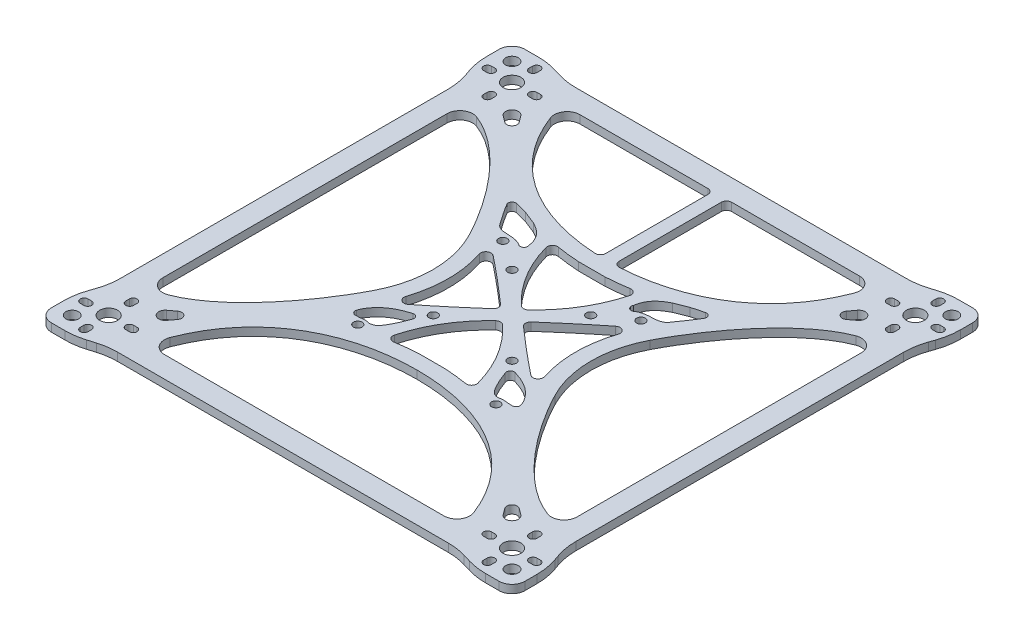
SolidWorks part; units mm, degrees
ref_plane "Front Plane" through (0, 0, 0) normal (0, 0, 1) x (1, 0, 0)
ref_plane "Top Plane" through (0, 0, 0) normal (0, 1, 0) x (1, 0, 0)
ref_plane "Right Plane" through (0, 0, 0) normal (1, 0, 0) x (0, 0, -1)
sketch "Sketch2" plane through (0, 0, 0) normal (0, 1, 0) x (1, 0, 0)
  line L1 (-91.75, 91.75) -> (91.75, 91.75)
  line L2 (-91.75, 91.75) -> (-91.75, -91.75)
  line L3 (-91.75, -91.75) -> (91.75, -91.75)
  line L4 (91.75, 91.75) -> (91.75, -91.75)
  line L5 (-91.75, 91.75) -> (91.75, -91.75) construction
  line L6 (-91.75, -91.75) -> (91.75, 91.75) construction
  point P0 (0, 0)
  dimension "D1" = 183.5
extrude "Base size" add sketch "Sketch2" along normal blind 3.15
sketch "Sketch3" plane through (0, 3.15, 0) normal (0, 1, 0) x (1, 0, 0)
  line L0 (-91.75, 91.75) -> (-91.75, -91.75) construction
  line L1 (80.25, 80.5) -> (-80.25, 80.5)
  line L2 (80.25, 80.5) -> (80.25, -80.5)
  line L3 (80.25, -80.5) -> (-80.25, -80.5)
  line L4 (-80.25, 80.5) -> (-80.25, -80.5)
  line L5 (80.25, 80.5) -> (-80.25, -80.5) construction
  line L6 (80.25, -80.5) -> (-80.25, 80.5) construction
  line L7 (0, 91.75) -> (0, -91.75) construction
  line L8 (-91.75, 0) -> (91.75, 0) construction
  line L9 (-91.75, -88.75) -> (91.75, -88.75)
  line L10 (80.25, 61.3098) -> (-80.25, -61.3098) construction
  line L11 (-91.75, 36.75) -> (91.75, 36.75) construction
  line L12 (88.25, 91.75) -> (88.25, -91.75)
  line L13 (91.75, -91.75) -> (91.75, 91.75) construction
  line L14 (-77.75, 91.75) -> (-67.75, 88.75)
  line L15 (-91.75, 77.75) -> (-88.25, 67.75)
  line L16 (-67.75, 88.75) -> (-67.75, 80.5) construction
  line L17 (-91.75, 88.75) -> (91.75, 88.75)
  line L18 (-88.25, 91.75) -> (-88.25, -91.75)
  line L19 (91.75, 91.75) -> (-91.75, 91.75) construction
  line L20 (-91.75, -91.75) -> (91.75, -91.75) construction
  line L21 (-67.75, 84.625) -> (-77.75, 84.625) construction
  line L22 (-77.75, 91.75) -> (-77.75, 80.5) construction
  line L23 (-91.75, 77.75) -> (-80.25, 77.75) construction
  line L24 (-88.25, 67.75) -> (-80.25, 67.75) construction
  line L25 (-84.25, 67.75) -> (-84.25, 77.75) construction
  line L26 (77.75, 91.75) -> (67.75, 88.75)
  line L27 (91.75, 77.75) -> (88.25, 67.75)
  line L28 (91.75, -77.75) -> (88.25, -67.75)
  line L29 (77.75, -91.75) -> (67.75, -88.75)
  line L30 (-77.75, -91.75) -> (-67.75, -88.75)
  line L31 (-91.75, -77.75) -> (-88.25, -67.75)
  line L32 (-61, 80.5) -> (61, -80.5) construction
  line L33 (61, 80.5) -> (-61, -80.5) construction
  line L34 (0, 36.75) -> (0, -36.75)
  line L35 (-28, 0) -> (28, 0)
  line L36 (2.6, 80.5) -> (2.6, 36.7902)
  line L37 (28, 80.5) -> (28, -91.75) construction
  line L38 (-61, 80.5) -> (61, 80.5) construction
  line L39 (-2.6, 80.5) -> (-2.6, 36.7902)
  line L40 (-80.3099, 61.2501) -> (80.3099, -61.2501) construction
  line L41 (80.25, 61.3098) -> (80.3099, -61.2501) construction
  line L42 (61, 80.5) -> (80.25, 61.3098) construction
  line L43 (-84.25, 77.75) -> (-84.25, 91.75) construction
  line L44 (-77.75, 84.625) -> (-91.75, 84.625) construction
  line L45 (-61, -80.5) -> (-61, -88.75) construction
  line L46 (61, -80.5) -> (61, -88.75) construction
  line L47 (-61, -84.625) -> (61, -84.625) construction
  line L48 (34.054, 44.9401) -> (44.8339, 34.1936) construction
  spline S0 degree 3 poles (61, 80.5) (52.8169, 49.5684) (26.9144, 36.75) (0, 36.75) knots 0 0 0 0 1 1 1 1
  spline S1 degree 3 poles (80.25, 61.3098) (57.9285, 59.6828) (32.235, 20.0435) (28, 0) knots 0 0 0 0 1 1 1 1
  spline S2 degree 3 poles (-61, 80.5) (-52.8169, 49.5684) (-26.9144, 36.75) (0, 36.75) knots 0 0 0 0 1 1 1 1
  spline S3 degree 3 poles (-61, -80.5) (-52.8169, -49.5684) (-26.9144, -36.75) (0, -36.75) knots 0 0 0 0 1 1 1 1
  spline S4 degree 3 poles (61, -80.5) (52.8169, -49.5684) (26.9144, -36.75) (0, -36.75) knots 0 0 0 0 1 1 1 1
  spline S5 degree 3 poles (80.25, -61.3098) (57.9285, -59.6828) (32.235, -20.0435) (28, 0) knots 0 0 0 0 1 1 1 1
  spline S6 degree 3 poles (-80.25, 61.3098) (-57.9285, 59.6828) (-32.235, 20.0435) (-28, 0) knots 0 0 0 0 1 1 1 1
  spline S7 degree 3 poles (-80.25, -61.3098) (-57.9285, -59.6828) (-32.235, -20.0435) (-28, 0) knots 0 0 0 0 1 1 1 1
  point P0 (0, 0)
  point P82 (39.444, 39.5668)
  line M13 (91.75, -91.75) -> (91.75, 91.75)
  line M14 (91.75, 91.75) -> (-91.75, 91.75)
  line M15 (-91.75, 91.75) -> (-91.75, -91.75)
  line M16 (-91.75, -91.75) -> (91.75, -91.75)
  dimension "D2" = 176.5
  dimension "D3" = 177.5
  dimension "D4" = 10
  dimension "D5" = 14
  dimension "D6" = 5.2
  dimension "D7" = 122
  dimension "D8" = 73.5
  dimension "D9" = 8.25
  dimension "D10" = 8
  dimension "D11" = 56
extrude "Base outline and pockets" cut sketch "Sketch3" against normal up to next contours L1 S2 L39 | S0 L1 L36 | L26 L14 L17 M14 | L4 | L2 S1 | L3 S4 S3 | L31 L18 L15 M15 | L30 L29 L9 M16 | L28 L27 L12 M13 region at (26.4341, 3.15, -62.2428) region at (60.1835, 3.15, 0) region at (-26.4341, 3.15, -62.2428) region at (0, 3.15, 62.0397) region at (-60.1835, 3.15, 0) region at (0, 3.15, 90.2844) region at (-90.0401, 3.15, 0) region at (90.0401, 3.15, 0) region at (0, 3.15, -90.2844)
sketch "Sketch4" plane through (0, 3.15, 0) normal (0, 1, 0) x (1, 0, 0)
  line L0 (0, 88.75) -> (0, -88.75) construction
  line L1 (-67.75, 88.75) -> (67.75, 88.75) construction
  line L2 (-67.75, -88.75) -> (67.75, -88.75) construction
  line L3 (-88.25, 0) -> (88.25, 0) construction
  line L4 (-88.25, 67.75) -> (-88.25, -67.75) construction
  line L5 (88.25, 67.75) -> (88.25, -67.75) construction
  line L6 (91.75, 91.75) -> (-91.75, -91.75) construction
  line L7 (-91.75, 91.75) -> (91.75, -91.75) construction
  line L8 (74.6853, 78.1353) -> (81.5853, 78.1353) construction
  line L9 (60.3295, 78.1353) -> (91.8849, 78.1353) construction
  line L10 (91.75, 77.75) -> (88.25, 67.75) construction
  line L11 (78.1353, 91.8656) -> (78.1353, 61.0454) construction
  line L12 (77.75, 91.75) -> (67.75, 88.75) construction
  line L13 (68.6353, 78.1353) -> (70.0103, 78.1353) construction
  line L14 (68.6353, 79.6353) -> (70.0103, 79.6353)
  line L15 (68.6353, 76.6353) -> (70.0103, 76.6353)
  line L16 (71.5103, 78.1353) -> (71.5103, 76.6353) construction
  line L17 (71.5103, 76.6353) -> (67.1353, 76.6353) construction
  line L18 (67.1353, 78.1353) -> (67.1353, 76.6353) construction
  line L19 (87.6353, 78.1353) -> (86.2603, 78.1353) construction
  line L20 (87.6353, 79.6353) -> (86.2603, 79.6353)
  line L21 (87.6353, 76.6353) -> (86.2603, 76.6353)
  line L22 (78.1353, 68.6353) -> (78.1353, 70.0103) construction
  line L23 (79.6353, 68.6353) -> (79.6353, 70.0103)
  line L24 (76.6353, 68.6353) -> (76.6353, 70.0103)
  line L25 (78.1353, 87.6353) -> (78.1353, 86.2603) construction
  line L26 (79.6353, 87.6353) -> (79.6353, 86.2603)
  line L27 (76.6353, 87.6353) -> (76.6353, 86.2603)
  line L28 (-68.6353, 78.1353) -> (-70.0103, 78.1353) construction
  line L29 (-68.6353, 79.6353) -> (-70.0103, 79.6353)
  line L30 (-68.6353, 76.6353) -> (-70.0103, 76.6353)
  line L31 (-78.1353, 87.6353) -> (-78.1353, 86.2603) construction
  line L32 (-79.6353, 87.6353) -> (-79.6353, 86.2603)
  line L33 (-76.6353, 87.6353) -> (-76.6353, 86.2603)
  line L34 (-87.6353, 78.1353) -> (-86.2603, 78.1353) construction
  line L35 (-87.6353, 79.6353) -> (-86.2603, 79.6353)
  line L36 (-87.6353, 76.6353) -> (-86.2603, 76.6353)
  line L37 (-78.1353, 68.6353) -> (-78.1353, 70.0103) construction
  line L38 (-79.6353, 68.6353) -> (-79.6353, 70.0103)
  line L39 (-76.6353, 68.6353) -> (-76.6353, 70.0103)
  line L40 (-87.6353, -78.1353) -> (-86.2603, -78.1353) construction
  line L41 (-87.6353, -79.6353) -> (-86.2603, -79.6353)
  line L42 (-87.6353, -76.6353) -> (-86.2603, -76.6353)
  line L43 (-78.1353, -68.6353) -> (-78.1353, -70.0103) construction
  line L44 (-79.6353, -68.6353) -> (-79.6353, -70.0103)
  line L45 (-76.6353, -68.6353) -> (-76.6353, -70.0103)
  line L46 (-68.6353, -78.1353) -> (-70.0103, -78.1353) construction
  line L47 (-68.6353, -79.6353) -> (-70.0103, -79.6353)
  line L48 (-68.6353, -76.6353) -> (-70.0103, -76.6353)
  line L49 (-78.1353, -87.6353) -> (-78.1353, -86.2603) construction
  line L50 (-79.6353, -87.6353) -> (-79.6353, -86.2603)
  line L51 (-76.6353, -87.6353) -> (-76.6353, -86.2603)
  line L52 (68.6353, -78.1353) -> (70.0103, -78.1353) construction
  line L53 (68.6353, -79.6353) -> (70.0103, -79.6353)
  line L54 (68.6353, -76.6353) -> (70.0103, -76.6353)
  line L55 (78.1353, -87.6353) -> (78.1353, -86.2603) construction
  line L56 (79.6353, -87.6353) -> (79.6353, -86.2603)
  line L57 (76.6353, -87.6353) -> (76.6353, -86.2603)
  line L58 (87.6353, -78.1353) -> (86.2603, -78.1353) construction
  line L59 (87.6353, -79.6353) -> (86.2603, -79.6353)
  line L60 (87.6353, -76.6353) -> (86.2603, -76.6353)
  line L61 (78.1353, -68.6353) -> (78.1353, -70.0103) construction
  line L62 (79.6353, -68.6353) -> (79.6353, -70.0103)
  line L63 (76.6353, -68.6353) -> (76.6353, -70.0103)
  circle A0 centre (78.1353, 78.1353) radius 3.45
  arc A1 (68.6353, 79.6353) -> (68.6353, 76.6353) centre (68.6353, 78.1353) ccw
  arc A2 (70.0103, 76.6353) -> (70.0103, 79.6353) centre (70.0103, 78.1353) ccw
  arc A3 (87.6353, 79.6353) -> (87.6353, 76.6353) centre (87.6353, 78.1353) cw
  arc A4 (86.2603, 76.6353) -> (86.2603, 79.6353) centre (86.2603, 78.1353) cw
  arc A5 (79.6353, 68.6353) -> (76.6353, 68.6353) centre (78.1353, 68.6353) cw
  arc A6 (76.6353, 70.0103) -> (79.6353, 70.0103) centre (78.1353, 70.0103) cw
  arc A7 (79.6353, 87.6353) -> (76.6353, 87.6353) centre (78.1353, 87.6353) ccw
  arc A8 (76.6353, 86.2603) -> (79.6353, 86.2603) centre (78.1353, 86.2603) ccw
  arc A9 (-68.6353, 79.6353) -> (-68.6353, 76.6353) centre (-68.6353, 78.1353) cw
  arc A10 (-70.0103, 76.6353) -> (-70.0103, 79.6353) centre (-70.0103, 78.1353) cw
  arc A11 (-79.6353, 87.6353) -> (-76.6353, 87.6353) centre (-78.1353, 87.6353) cw
  arc A12 (-76.6353, 86.2603) -> (-79.6353, 86.2603) centre (-78.1353, 86.2603) cw
  arc A13 (-87.6353, 79.6353) -> (-87.6353, 76.6353) centre (-87.6353, 78.1353) ccw
  arc A14 (-86.2603, 76.6353) -> (-86.2603, 79.6353) centre (-86.2603, 78.1353) ccw
  arc A15 (-79.6353, 68.6353) -> (-76.6353, 68.6353) centre (-78.1353, 68.6353) ccw
  arc A16 (-76.6353, 70.0103) -> (-79.6353, 70.0103) centre (-78.1353, 70.0103) ccw
  circle A17 centre (-78.1353, 78.1353) radius 3.45
  arc A18 (-87.6353, -79.6353) -> (-87.6353, -76.6353) centre (-87.6353, -78.1353) cw
  arc A19 (-86.2603, -76.6353) -> (-86.2603, -79.6353) centre (-86.2603, -78.1353) cw
  arc A20 (-79.6353, -68.6353) -> (-76.6353, -68.6353) centre (-78.1353, -68.6353) cw
  arc A21 (-76.6353, -70.0103) -> (-79.6353, -70.0103) centre (-78.1353, -70.0103) cw
  arc A22 (-68.6353, -79.6353) -> (-68.6353, -76.6353) centre (-68.6353, -78.1353) ccw
  arc A23 (-70.0103, -76.6353) -> (-70.0103, -79.6353) centre (-70.0103, -78.1353) ccw
  arc A24 (-79.6353, -87.6353) -> (-76.6353, -87.6353) centre (-78.1353, -87.6353) ccw
  arc A25 (-76.6353, -86.2603) -> (-79.6353, -86.2603) centre (-78.1353, -86.2603) ccw
  arc A26 (68.6353, -79.6353) -> (68.6353, -76.6353) centre (68.6353, -78.1353) cw
  arc A27 (70.0103, -76.6353) -> (70.0103, -79.6353) centre (70.0103, -78.1353) cw
  arc A28 (79.6353, -87.6353) -> (76.6353, -87.6353) centre (78.1353, -87.6353) cw
  arc A29 (76.6353, -86.2603) -> (79.6353, -86.2603) centre (78.1353, -86.2603) cw
  arc A30 (87.6353, -79.6353) -> (87.6353, -76.6353) centre (87.6353, -78.1353) ccw
  arc A31 (86.2603, -76.6353) -> (86.2603, -79.6353) centre (86.2603, -78.1353) ccw
  arc A32 (79.6353, -68.6353) -> (76.6353, -68.6353) centre (78.1353, -68.6353) ccw
  arc A33 (76.6353, -70.0103) -> (79.6353, -70.0103) centre (78.1353, -70.0103) ccw
  circle A34 centre (78.1353, -78.1353) radius 3.45
  circle A35 centre (-78.1353, -78.1353) radius 3.45
  spline S0 degree 3 poles (61, 80.5) (53.0808, 50.5659) (28.5665, 37.5955) (2.6, 36.7902) knots 0 0 0 0 0.967753 0.967753 0.967753 0.967753 construction
  spline S1 degree 3 poles (80.25, 61.3098) (57.9285, 59.6828) (32.235, 20.0435) (28, 0) knots 0 0 0 0 1 1 1 1 construction
  point P42 (69.3228, 78.1353)
  point P53 (86.9478, 78.1353)
  point P60 (78.1353, 69.3228)
  point P67 (78.1353, 86.9478)
  point P74 (-69.3228, 78.1353)
  point P81 (-78.1353, 86.9478)
  point P88 (-86.9478, 78.1353)
  point P95 (-78.1353, 69.3228)
  point P104 (-86.9478, -78.1353)
  point P111 (-78.1353, -69.3228)
  point P118 (-69.3228, -78.1353)
  point P125 (-78.1353, -86.9478)
  point P132 (69.3228, -78.1353)
  point P139 (78.1353, -86.9478)
  point P146 (86.9478, -78.1353)
  point P153 (78.1353, -69.3228)
  dimension "D1" = 6.9
  dimension "D5" = 1.5
  dimension "D2" = 221
  dimension "D3" = 13.25
  dimension "D4" = 22
extrude "Motor holes" cut sketch "Sketch4" against normal up to next
sketch "Sketch5" plane through (0, 3.15, 0) normal (0, 1, 0) x (1, 0, 0)
  line L0 (-91.75, -91.75) -> (91.75, 91.75) construction
  line L1 (-91.75, 91.75) -> (91.75, -91.75) construction
  line L2 (-28, 0) -> (28, 0) construction
  line L3 (0, 88.75) -> (0, -88.75) construction
  line L4 (-26.75, 23.1997) -> (26.75, 23.1997)
  line L5 (-26.75, 23.1997) -> (-26.75, -33.0003)
  line L6 (-26.75, -33.0003) -> (26.75, -33.0003)
  line L7 (26.75, 23.1997) -> (26.75, -33.0003)
  line L8 (-26.75, 23.1997) -> (26.75, -33.0003) construction
  line L9 (-26.75, -33.0003) -> (26.75, 23.1997) construction
  line L10 (-67.75, 88.75) -> (67.75, 88.75) construction
  line L11 (-67.75, -88.75) -> (67.75, -88.75) construction
  line L12 (16.1608, -16.6558) -> (25.8392, -31.5945)
  line L13 (15.25, -15.25) -> (26.75, -33.0003) construction
  circle A0 centre (15.25, 15.25) radius 1.675
  circle A1 centre (-15.25, -15.25) radius 1.675
  circle A2 centre (-15.25, 15.25) radius 1.675
  circle A3 centre (15.25, -15.25) radius 1.675
  circle A4 centre (-26.75, 23.1997) radius 1.675
  circle A5 centre (26.75, 23.1997) radius 1.675
  circle A6 centre (26.75, -33.0003) radius 1.675
  circle A7 centre (-26.75, -33.0003) radius 1.675
  point P20 (0, -4.9003)
  dimension "D1" = 3.35
  dimension "D2" = 30.5
  dimension "D3" = 53.5
  dimension "D4" = 56.2
  dimension "D5" = 17.8
extrude "FC holes" cut sketch "Sketch5" against normal up to next contours L4 A4 L5 | L5 A4 L4 | A2 | A0 | L7 A5 L4 | L4 A5 L7 | L6 A6 L7 | L7 A6 L6 | A3 | A1 | L5 A7 L6 | L6 A7 L5 region at (-26.987, 3.15, -23.4367) region at (-26.0391, 3.15, -22.4888) region at (15.25, 3.15, 15.25) region at (26.987, 3.15, -23.4367) region at (26.0391, 3.15, -22.4888) region at (-26.0391, 3.15, 32.2894) region at (-26.987, 3.15, 33.2372) region at (26.987, 3.15, 33.2372) region at (26.0391, 3.15, 32.2894) region at (15.25, 3.15, -15.25) region at (-15.25, 3.15, 15.25) region at (-15.25, 3.15, -15.25)
sketch "Sketch6" plane through (0, 3.15, 0) normal (0, 1, 0) x (1, 0, 0)
  line L0 (-91.75, 91.75) -> (91.75, -91.75) construction
  line L1 (-91.75, -91.75) -> (91.75, 91.75) construction
  line L2 (0, 88.75) -> (0, -88.75) construction
  line L3 (-67.75, 88.75) -> (67.75, 88.75) construction
  line L4 (-67.75, -88.75) -> (67.75, -88.75) construction
  line L5 (-88.25, 0) -> (88.25, 0) construction
  line L6 (-88.25, 67.75) -> (-88.25, -67.75) construction
  line L7 (88.25, 67.75) -> (88.25, -67.75) construction
  line L8 (63.5689, 63.5689) -> (68.9429, 68.9429) construction
  line L9 (65.2484, 68.6777) -> (63.3814, 66.1808)
  line L10 (66.1808, 63.3814) -> (68.6777, 65.2484)
  line L11 (-63.3814, -66.1808) -> (-65.2484, -68.6777)
  line L12 (-68.6777, -65.2484) -> (-66.1808, -63.3814)
  line L13 (65.2484, -68.6777) -> (63.3814, -66.1808)
  line L14 (66.1808, -63.3814) -> (68.6777, -65.2484)
  line L15 (-68.6777, 65.2484) -> (-66.1808, 63.3814)
  line L16 (-63.3814, 66.1808) -> (-65.2484, 68.6777)
  circle A0 centre (-85.2064, 85.2064) radius 2.45
  circle A1 centre (85.2064, 85.2064) radius 2.45
  circle A2 centre (85.2064, -85.2064) radius 2.45
  circle A3 centre (-85.2064, -85.2064) radius 2.45
  circle A4 centre (67.2105, 67.2105) radius 2.45
  circle A5 centre (64.9831, 64.9831) radius 2
  circle A6 centre (-64.9831, -64.9831) radius 2
  circle A7 centre (-67.2105, -67.2105) radius 2.45
  circle A8 centre (67.2105, -67.2105) radius 2.45
  circle A9 centre (64.9831, -64.9831) radius 2
  circle A10 centre (-64.9831, 64.9831) radius 2
  circle A11 centre (-67.2105, 67.2105) radius 2.45
  circle A12 centre (78.1353, 78.1353) radius 3.45 construction
  dimension "D1" = 4.9
  dimension "D3" = 7.6
  dimension "D4" = 4
  dimension "D2" = 10
  dimension "D5" = 195
extrude "Motor wire holes" cut sketch "Sketch6" against normal up to next contours A0 | A10 A11 | A10 A11 | A11 A10 | A1 | A5 A4 | A4 A5 | A5 A4 | A2 | A8 A9 | A9 A8 | A9 A8 | L14 A9 A8 | A8 A9 L13 | A3 | A7 A6 | A6 A7 | A7 A6 | L12 A7 A6 | A6 A7 L11 | A11 L15 A10 | A11 A10 L16 | A5 A4 L9 | A5 L10 A4 region at (64.438, 3.15, -67.2832) region at (67.4336, 3.15, -67.4336) region at (64.7131, 3.15, -64.7131) region at (65.9277, 3.15, -65.9277) region at (67.2832, 3.15, -64.438) region at (-64.7131, 3.15, 64.7131) region at (-64.438, 3.15, 67.2832) region at (-67.4336, 3.15, 67.4336) region at (-65.9277, 3.15, 65.9277) region at (-67.2832, 3.15, 64.438) region at (67.4336, 3.15, 67.4336) region at (64.438, 3.15, 67.2832) region at (64.7131, 3.15, 64.7131) region at (65.9277, 3.15, 65.9277) region at (67.2832, 3.15, 64.438) region at (-67.2832, 3.15, -64.438) region at (-67.4336, 3.15, -67.4336) region at (-64.7131, 3.15, -64.7131) region at (-64.438, 3.15, -67.2832) region at (-65.9277, 3.15, -65.9277) region at (-85.2064, 3.15, -85.2064) region at (85.2064, 3.15, -85.2064) region at (85.2064, 3.15, 85.2064) region at (-85.2064, 3.15, 85.2064)
fillet "Large pocket fillet" radius 40 2 edges at (28, 1.575, 0) (-28, 1.575, 0)
fillet "Outside edge fillet" radius 25 16 edges at (-88.25, 1.575, 67.75) (-91.75, 1.575, 77.75) (-88.25, 1.575, -67.75) (-91.75, 1.575, -77.75) (-77.75, 1.575, -91.75) (-67.75, 1.575, -88.75) (67.75, 1.575, -88.75) (77.75, 1.575, -91.75) (91.75, 1.575, -77.75) (88.25, 1.575, -67.75) (88.25, 1.575, 67.75) (91.75, 1.575, 77.75) (77.75, 1.575, 91.75) (67.75, 1.575, 88.75) (-67.75, 1.575, 88.75) (-77.75, 1.575, 91.75)
fillet "Inner pocket fillet" radius 5 12 edges at (80.25, 1.575, 61.3098) (80.25, 1.575, -61.3098) (-80.25, 1.575, 61.3098) (-80.25, 1.575, -61.3098) (-61, 1.575, 80.5) (61, 1.575, 80.5) (61, 1.575, -80.5) (-61, 1.575, -80.5) (-91.75, 1.575, -91.75) (91.75, 1.575, -91.75) (91.75, 1.575, 91.75) (-91.75, 1.575, 91.75)
fillet "Small pocket fillet" radius 2 4 edges at (-2.6, 1.575, -36.7902) (2.6, 1.575, -36.7902) (2.6, 1.575, -80.5) (-2.6, 1.575, -80.5)
sketch "Sketch7" plane through (0, 3.15, 0) normal (0, 1, 0) x (1, 0, 0)
  line L0 (-16.925, 38.5516) -> (-16.925, -38.5516) construction
  line L1 (0, 88.75) -> (0, -88.75) construction
  line L2 (-64.0808, 88.75) -> (64.0808, 88.75) construction
  line L3 (-64.0808, -88.75) -> (64.0808, -88.75) construction
  line L4 (-88.25, 0) -> (88.25, 0) construction
  line L5 (-88.25, 63.5014) -> (-88.25, -63.5014) construction
  line L6 (88.25, 63.5014) -> (88.25, -63.5014) construction
  line L7 (-5.0538, 30.8925) -> (5.0538, 30.8925)
  line L8 (-90.2855, -90.2855) -> (90.2855, 90.2855) construction
  line L9 (90.2855, -90.2855) -> (-90.2855, 90.2855) construction
  line L10 (-16.925, 10.8936) -> (-10.9183, 16.9003) construction
  line L11 (-4.25, 3.75) -> (4.25, 3.75)
  line L12 (-4.25, 3.75) -> (-4.25, -3.75)
  line L13 (-4.25, -3.75) -> (4.25, -3.75)
  line L14 (4.25, 3.75) -> (4.25, -3.75)
  line L15 (-4.25, 3.75) -> (4.25, -3.75) construction
  line L16 (-4.25, -3.75) -> (4.25, 3.75) construction
  line L17 (-5.0538, -30.8925) -> (5.0538, -30.8925)
  line L20 (-34.8215, 16.925) -> (34.391, 16.925) construction
  line L21 (15.25, 15.25) -> (15.25, -15.25) construction
  line L22 (90.2855, 90.2855) -> (-88.25, -12.0526) construction
  line L23 (-88.25, 63.5014) -> (-88.25, -63.5014) construction
  line L24 (-26.75, 23.1997) -> (26.75, 23.1997) construction
  line L25 (-88.25, 36.8829) -> (88.25, 36.8829) construction
  line L26 (88.25, 63.5014) -> (88.25, -63.5014) construction
  circle A0 centre (-21.5445, 26.1835) radius 1.5
  circle A1 centre (-15.25, 15.25) radius 1.675 construction
  arc A2 (29.7964, -21.1732) -> (29.7964, 21.1732) centre (70.6339, 0) cw
  arc A3 (-29.7964, -21.1732) -> (-29.7964, 21.1732) centre (-70.6339, 0) ccw
  arc A4 (-29.7964, -21.1732) -> (-29.7964, 21.1732) centre (-70.6339, 0) ccw
  arc A5 (-91.75, -86.75) -> (-86.75, -91.75) centre (-86.75, -86.75) ccw construction
  arc A6 (91.75, 86.75) -> (86.75, 91.75) centre (86.75, 86.75) ccw construction
  arc A7 (86.75, -91.75) -> (91.75, -86.75) centre (86.75, -86.75) ccw construction
  arc A8 (-86.75, 91.75) -> (-91.75, 86.75) centre (-86.75, 86.75) ccw construction
  circle A9 centre (-36.9396, 36.9396) radius 1.5
  circle A10 centre (21.5445, 26.1835) radius 1.5
  circle A11 centre (36.9396, 36.9396) radius 1.5
  circle A12 centre (-19.4019, -20.031) radius 1.5
  circle A13 centre (-30.4025, -28.806) radius 1.5
  circle A14 centre (19.4019, -20.031) radius 1.5
  circle A15 centre (30.4025, -28.806) radius 1.5
  arc A20 (35.1231, 18.4115) -> (35.1231, -18.4115) centre (70.6339, 0) ccw construction
  spline S0 degree 3 poles (1646.3229, 1054.028) (81.128, 560.1113) (-122.2034, 169.5598) (-58.2555, 59.2518) (-56.365, 56.5397) (-52.2443, 51.5404) (-50.0144, 49.2533) (-45.2746, 45.1018) (-42.7649, 43.2373) (-34.9047, 38.2598) (-29.2265, 35.7639) (128.467, -11.0091) (434.3868, 432.3515) (-1986.9742, -2.3886) knots -4.46889 -4.46889 -4.46889 -4.46889 0.125 0.125 0.25 0.25 0.375 0.375 0.5 0.5 0.75 0.75 7.170137 7.170137 7.170137 7.170137 only from (-64.4192, 71.565) to (-5.0538, 30.8925)
  spline S1 degree 3 poles (-64.4192, 71.565) (-63.1407, 68.2274) (-61.6434, 65.0957) (-58.2555, 59.2518) (-56.365, 56.5397) (-52.2443, 51.5404) (-50.0144, 49.2533) (-45.2746, 45.1018) (-42.7649, 43.2373) (-34.9047, 38.2598) (-29.2265, 35.7639) (-17.4057, 32.2577) (-11.2615, 31.2452) (-5.0538, 30.8925) knots 0 0 0 0 0.125 0.125 0.25 0.25 0.375 0.375 0.5 0.5 0.75 0.75 1 1 1 1
  spline S2 degree 3 poles (64.4192, 71.565) (63.1407, 68.2274) (61.6434, 65.0957) (58.2555, 59.2518) (56.365, 56.5397) (52.2443, 51.5404) (50.0144, 49.2533) (45.2746, 45.1018) (42.7649, 43.2373) (34.9047, 38.2598) (29.2265, 35.7639) (17.4057, 32.2577) (11.2615, 31.2452) (5.0538, 30.8925) knots 0 0 0 0 0.125 0.125 0.25 0.25 0.375 0.375 0.5 0.5 0.75 0.75 1 1 1 1
  spline S3 degree 2 poles (-16.925, 32.417) (-13.1474, 15.3314) (0, 3.75) knots 0 0 0 1 1 1
  spline S4 degree 3 poles (64.4192, -71.565) (63.1407, -68.2274) (61.6434, -65.0957) (58.2555, -59.2518) (56.365, -56.5397) (52.2443, -51.5404) (50.0144, -49.2533) (45.2746, -45.1018) (42.7649, -43.2373) (34.9047, -38.2598) (29.2265, -35.7639) (17.4057, -32.2577) (11.2615, -31.2452) (5.0538, -30.8925) knots 0 0 0 0 0.125 0.125 0.25 0.25 0.375 0.375 0.5 0.5 0.75 0.75 1 1 1 1
  spline S5 degree 3 poles (-64.4192, -71.565) (-63.1407, -68.2274) (-61.6434, -65.0957) (-58.2555, -59.2518) (-56.365, -56.5397) (-52.2443, -51.5404) (-50.0144, -49.2533) (-45.2746, -45.1018) (-42.7649, -43.2373) (-34.9047, -38.2598) (-29.2265, -35.7639) (-17.4057, -32.2577) (-11.2615, -31.2452) (-5.0538, -30.8925) knots 0 0 0 0 0.125 0.125 0.25 0.25 0.375 0.375 0.5 0.5 0.75 0.75 1 1 1 1
  spline S8 degree 3 poles (-1134.0161, 1685.3643) (-49.3729, -207.5723) (26.6814, -60.6672) (-40.7855, 39.0077) (-44.0849, 43.3226) (-49.3783, 49.2973) (-51.2004, 51.206) (-54.9484, 54.8014) (-56.8742, 56.4883) (-60.8255, 59.5815) (-62.8511, 60.988) (-130.4494, 101.0329) (-249.7376, -33.0626) (-622.9532, -1852.5469) knots -5.128274 -5.128274 -5.128274 -5.128274 0.25 0.25 0.5 0.5 0.625 0.625 0.75 0.75 0.875 0.875 4.813958 4.813958 4.813958 4.813958 only from (-29.7964, 21.1732) to (-71.3367, 65.3441)
  spline S9 degree 3 poles (-622.9539, 1852.5503) (-249.7378, 33.0628) (-130.4494, -101.0329) (-62.8511, -60.988) (-60.8255, -59.5815) (-56.8742, -56.4883) (-54.9484, -54.8014) (-51.2004, -51.206) (-49.3783, -49.2973) (-44.0849, -43.3226) (-40.7855, -39.0077) (26.6809, 60.6663) (-49.3716, 207.5698) (-1133.9881, -1685.3155) knots -3.81396 -3.81396 -3.81396 -3.81396 0.125 0.125 0.25 0.25 0.375 0.375 0.5 0.5 0.75 0.75 6.128227 6.128227 6.128227 6.128227 only from (-71.3367, -65.3441) to (-29.7964, -21.1732)
  spline S10 degree 3 poles (-29.7964, 21.1732) (-32.0988, 25.6138) (-34.7919, 30.1529) (-40.7855, 39.0077) (-44.0849, 43.3226) (-49.3783, 49.2973) (-51.2004, 51.206) (-54.9484, 54.8014) (-56.8742, 56.4883) (-60.8255, 59.5815) (-62.8511, 60.988) (-67.0095, 63.4515) (-69.1429, 64.509) (-71.3367, 65.3441) knots 0 0 0 0 0.25 0.25 0.5 0.5 0.625 0.625 0.75 0.75 0.875 0.875 1 1 1 1
  spline S11 degree 3 poles (-71.3367, -65.3441) (-69.1429, -64.509) (-67.0095, -63.4515) (-62.8511, -60.988) (-60.8255, -59.5815) (-56.8742, -56.4883) (-54.9484, -54.8014) (-51.2004, -51.206) (-49.3783, -49.2973) (-44.0849, -43.3226) (-40.7855, -39.0077) (-34.7919, -30.1529) (-32.0988, -25.6138) (-29.7964, -21.1732) knots 0 0 0 0 0.125 0.125 0.25 0.25 0.375 0.375 0.5 0.5 0.75 0.75 1 1 1 1
  spline S12 degree 3 poles (71.3367, -65.3441) (69.1429, -64.509) (67.0095, -63.4515) (62.8511, -60.988) (60.8255, -59.5815) (56.8742, -56.4883) (54.9484, -54.8014) (51.2004, -51.206) (49.3783, -49.2973) (44.0849, -43.3226) (40.7855, -39.0077) (34.7919, -30.1529) (32.0988, -25.6138) (29.7964, -21.1732) knots 0 0 0 0 0.125 0.125 0.25 0.25 0.375 0.375 0.5 0.5 0.75 0.75 1 1 1 1
  spline S13 degree 3 poles (29.7964, 21.1732) (32.0988, 25.6138) (34.7919, 30.1529) (40.7855, 39.0077) (44.0849, 43.3226) (49.3783, 49.2973) (51.2004, 51.206) (54.9484, 54.8014) (56.8742, 56.4883) (60.8255, 59.5815) (62.8511, 60.988) (67.0095, 63.4515) (69.1429, 64.509) (71.3367, 65.3441) knots 0 0 0 0 0.25 0.25 0.5 0.5 0.625 0.625 0.75 0.75 0.875 0.875 1 1 1 1
  spline S14 degree 2 poles (-4.25, 0) (-16.6416, 11.0472) (-29.7964, 21.1732) knots 0 0 0 1 1 1
  spline S15 degree 2 poles (-4.25, 0) (-16.6416, -11.0472) (-29.7964, -21.1732) knots 0 0 0 1 1 1
  spline S16 degree 2 poles (4.25, 0) (16.6416, 11.0472) (29.7964, 21.1732) knots 0 0 0 1 1 1
  spline S17 degree 2 poles (4.25, 0) (16.6416, -11.0472) (29.7964, -21.1732) knots 0 0 0 1 1 1
  spline S18 degree 3 poles (-21.9791, 24.7479) (-23.5878, 25.961) (-26.3725, 26.354) (-29.9957, 26.3605) (-32.2323, 27.1662) (-34.8801, 31.1932) (-36.8125, 33.6901) (-38.3665, 36.4772) knots 0 0 0 0 0.266776 0.366283 0.496008 0.55938 1 1 1 1
  spline S19 degree 3 poles (-20.2432, 26.9295) (-20.8297, 31.2566) (-26.2951, 35.6787) (-33.5009, 37.7311) (-36.6227, 38.4057) knots 0 0 0 0 0.515354 1 1 1 1
  spline S20 degree 3 poles (20.2432, 26.9295) (20.8297, 31.2566) (26.2951, 35.6787) (33.5009, 37.7311) (36.6227, 38.4057) knots 0 0 0 0 0.515354 1 1 1 1
  spline S21 degree 3 poles (21.9791, 24.7479) (23.5878, 25.961) (26.3725, 26.354) (29.9957, 26.3605) (32.2323, 27.1662) (34.8801, 31.1932) (36.8125, 33.6901) (38.3665, 36.4772) knots 0 0 0 0 0.266776 0.366283 0.496008 0.55938 1 1 1 1
  spline S22 degree 3 poles (-19.8388, -18.5961) (-22.3686, -19.3665) (-27.6569, -21.3902) (-31.4613, -26.6871) (-31.8655, -28.4753) knots 0 0 0 0 0.555172 1 1 1 1
  spline S23 degree 3 poles (-18.0503, -20.6816) (-18.9124, -23.2799) (-21.0529, -28.0893) (-23.1479, -30.0025) (-25.0795, -30.4588) (-26.0674, -30.0052) (-27.5923, -30.0995) (-29.0445, -30.305) (-29.8811, -30.306) (-30.4025, -30.306) knots 0 0 0 0 0.491044 0.606921 0.658583 0.729368 0.792681 0.893562 1 1 1 1
  spline S24 degree 3 poles (18.0503, -20.6816) (18.9124, -23.2799) (21.0529, -28.0893) (23.1479, -30.0025) (25.0795, -30.4588) (26.0674, -30.0052) (27.5923, -30.0995) (29.0445, -30.305) (29.8811, -30.306) (30.4025, -30.306) knots 0 0 0 0 0.491044 0.606921 0.658583 0.729368 0.792681 0.893562 1 1 1 1
  spline S25 degree 3 poles (19.8388, -18.5961) (22.3686, -19.3665) (27.6569, -21.3902) (31.4613, -26.6871) (31.8655, -28.4753) knots 0 0 0 0 0.555172 1 1 1 1
  spline S26 degree 2 poles (16.925, 32.417) (13.1474, 15.3314) (0, 3.75) knots 0 0 0 1 1 1
  spline S27 degree 2 poles (-16.925, -32.417) (-13.1474, -15.3314) (0, -3.75) knots 0 0 0 1 1 1
  spline S28 degree 2 poles (16.925, -32.417) (13.1474, -15.3314) (0, -3.75) knots 0 0 0 1 1 1
  spline S30 degree 3 poles (-58.8163, 73.7114) (-49.4768, 49.3311) (-27.8394, 38.1967) (-4.7134, 36.8829) knots 0.076565 0.076565 0.076565 0.076565 0.941454 0.941454 0.941454 0.941454 construction
  spline S31 degree 3 poles (-58.8163, -73.7114) (-48.8446, -47.6807) (-24.8537, -36.75) (0, -36.75) knots 0.076565 0.076565 0.076565 0.076565 1 1 1 1 construction
  point P63 (0, 0)
  dimension "D5" = 8.5
  dimension "D6" = 7.5
  dimension "D7" = 3
  dimension "D8" = 6
  dimension "D1" = 6
  dimension "D4" = 6
extrude "Inner pockets" cut sketch "Sketch7" against normal up to next contours S23 A12 S22 A13 | A13 | A12 | S18 A9 | A0 S19 S1 A9 S18 | S18 A0 | A11 S21 | A10 S21 A11 S20 S2 | A10 S21 | A14 | S25 A14 S24 A15 | A15 | S26 S2 L7 S1 S3 | S16 S17 A2 | S4 S28 S27 S5 L17 | S15 S14 A4 region at (0, 3.15, -21.1528) region at (-29.0578, 3.15, -31.4939) region at (29.0578, 3.15, -31.4944) region at (-21.5398, 3.15, -26.1908) region at (21.5398, 3.15, -26.1908) region at (-36.9374, 3.15, -36.9408) region at (-18.8047, 3.15, 0) region at (18.8047, 3.15, 0) region at (36.9374, 3.15, -36.9408) region at (0, 3.15, 21.1528) region at (-19.4019, 3.15, 20.031) region at (-18.4002, 3.15, 18.6789) region at (-24.6165, 3.15, 25.1257) region at (19.4019, 3.15, 20.031) region at (25.0559, 3.15, 25.4051)
fillet "Pocket fillet" radius 2 12 edges at (29.7964, 1.575, 21.1732) (-29.7964, 1.575, 21.1732) (4.25, 1.575, 0) (29.7964, 1.575, -21.1732) (-4.25, 1.575, 0) (-29.7964, 1.575, -21.1732) (0, 1.575, 3.75) (0, 1.575, -3.75)
sketch "Sketch8" plane through (0, 3.15, 0) normal (0, 1, 0) x (1, 0, 0)
  line L0 (-86.75, -91.75) -> (-81.4192, -91.75) construction
  line L1 (-91.75, 91.75) -> (0, 91.75)
  line L2 (-91.75, 91.75) -> (-91.75, -91.75)
  line L3 (-91.75, -91.75) -> (0, -91.75)
  line L4 (0, 91.75) -> (0, -91.75)
  line L5 (-91.75, -81.9986) -> (-91.75, -86.75) construction
extrude "Cut-Extrude6" [suppressed] cut sketch "Sketch8" against normal up to next
sketch "Sketch9" plane through (0, 3.15, 0) normal (0, 1, 0) x (1, 0, 0)
  line L0 (86.75, 91.75) -> (81.4192, 91.75) construction
  line L1 (91.75, 91.75) -> (0, 91.75)
  line L2 (91.75, 91.75) -> (91.75, -91.75)
  line L3 (91.75, -91.75) -> (0, -91.75)
  line L4 (0, 91.75) -> (0, -91.75)
  line L5 (91.75, 81.9986) -> (91.75, 86.75) construction
extrude "Cut-Extrude7" [suppressed] cut sketch "Sketch9" against normal offset from surface (2.65 mm away) 0.5 up to face at (-21.612, 0, 0)
